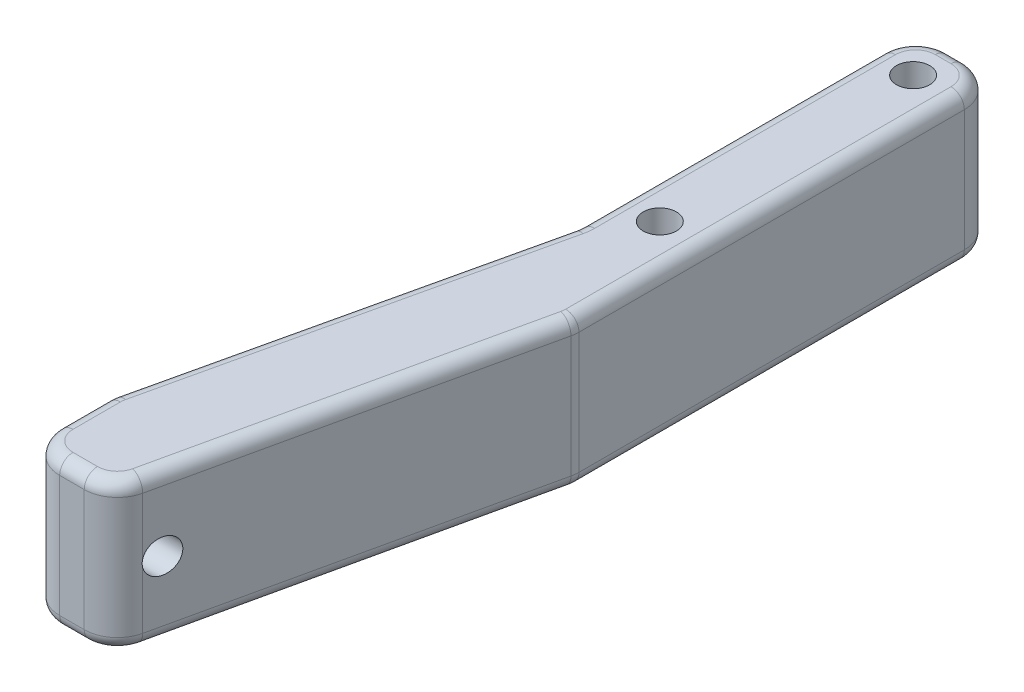
SolidWorks part; units mm, degrees
ref_plane "Front Plane" through (0, 0, 0) normal (0, 0, 1) x (1, 0, 0)
ref_plane "Top Plane" through (0, 0, 0) normal (0, 1, 0) x (1, 0, 0)
ref_plane "Right Plane" through (0, 0, 0) normal (1, 0, 0) x (0, 0, -1)
sketch "Sketch2" plane through (0, 0, 0) normal (0, 1, 0) x (1, 0, 0)
  line L0 (0, -63.5) -> (0, -114.3) construction
  line L1 (0, 0) -> (-12.35, 0)
  line L5 (-25.4, -120.65) -> (-12.7, -120.65)
  line L6 (0, -114.3) -> (0, -120.65) construction
  line L7 (0, -120.65) -> (-25.4, -120.65) construction
  line L14 (-12.35, 0) -> (-12.35, -50.8)
  line L15 (0, 0) -> (0, -63.5)
  line L19 (-25.4, -120.65) -> (-25.4, -107.95)
  line L22 (-12.7, -120.65) -> (0, -63.5)
  line L23 (-25.4, -107.95) -> (-12.35, -50.8)
  circle A0 centre (-6.35, -6.35) radius 2.5
  circle A1 centre (-6.35, -44.45) radius 2.5
  dimension "D4" = 5
  dimension "D6" = 38.1
  dimension "D7" = 5
  dimension "D2" = 6.35
  dimension "D3" = 6.35
  dimension "D5" = 6.35
  dimension "D8" = 63.5
  dimension "D9" = 107.95
  dimension "D10" = 6.35
  dimension "D11" = 25.4
  dimension "D12" = 6
  dimension "D13" = 12.7
  dimension "D14" = 50.8
extrude "Boss-Extrude1" add sketch "Sketch2" along normal blind 22.2504 contours L23 L19 L5 L22 L15 L1 L14 A1 A0 region at (-10.3111, 0, 64.0102)
sketch "Sketch3" plane through (-25.4, 0, 0) normal (-1, 0, 0) x (0, 0, 1)
  line L0 (120.65, 22.2504) -> (120.65, 0) construction
  line L1 (120.65, 22.2504) -> (107.95, 22.2504) construction
  line L2 (120.65, 0) -> (120.65, 22.2504)
  line L3 (120.65, 22.2504) -> (50.8, 22.2504)
  line L4 (50.8, 22.2504) -> (120.65, 16.1252)
  line L5 (120.65, 0) -> (50.8, 0)
  line L6 (50.8, 0) -> (120.65, 6.1252)
  circle A0 centre (114.3, 11.1252) radius 2.5
  dimension "D1" = 5
  dimension "D2" = 6.35
  dimension "D3" = 11.1252
  dimension "D4" = 10
  dimension "D5" = 5
extrude "Cut-Extrude1" cut sketch "Sketch3" against normal up to next contours A0 region at (-25.4, 11.1252, 114.3)
fillet "Fillet2" radius 5 7 edges at (0, 11.1252, 0) (0, 11.1252, 63.5) (-12.35, 11.1252, 0) (-12.35, 11.1252, 50.8) (-25.4, 11.1252, 107.95) (-25.4, 11.1252, 120.65) (-12.7, 11.1252, 120.65)
fillet "Fillet3" radius 2 28 edges at (-13.5822, 0, 119.5502) (-18.5554, 0, 120.65) (-23.9355, 0, 119.1855) (-25.4, 0, 112.0818) (-25.3685, 0, 107.9535) (-18.875, 0, 79.375) (-12.3815, 0, 50.7965) (-12.35, 0, 27.6182) (0, 0, 33.9756) (-0.0299, 0, 63.4967) (-13.5822, 22.2504, 119.5502) (-18.5554, 22.2504, 120.65) (-23.9355, 22.2504, 119.1855) (-25.4, 22.2504, 112.0818) (-25.3685, 22.2504, 107.9535) (-18.875, 22.2504, 79.375) (-12.3815, 22.2504, 50.7965) (-12.35, 22.2504, 27.6182) (0, 22.2504, 33.9756) (-0.0299, 22.2504, 63.4967) (-5.9745, 0, 90.3852) (-5.9745, 22.2504, 90.3852) (-10.8855, 0, 1.4645) (-6.175, 0, 0) (-1.4645, 0, 1.4645) (-10.8855, 22.2504, 1.4645) (-6.175, 22.2504, 0) (-1.4645, 22.2504, 1.4645)
